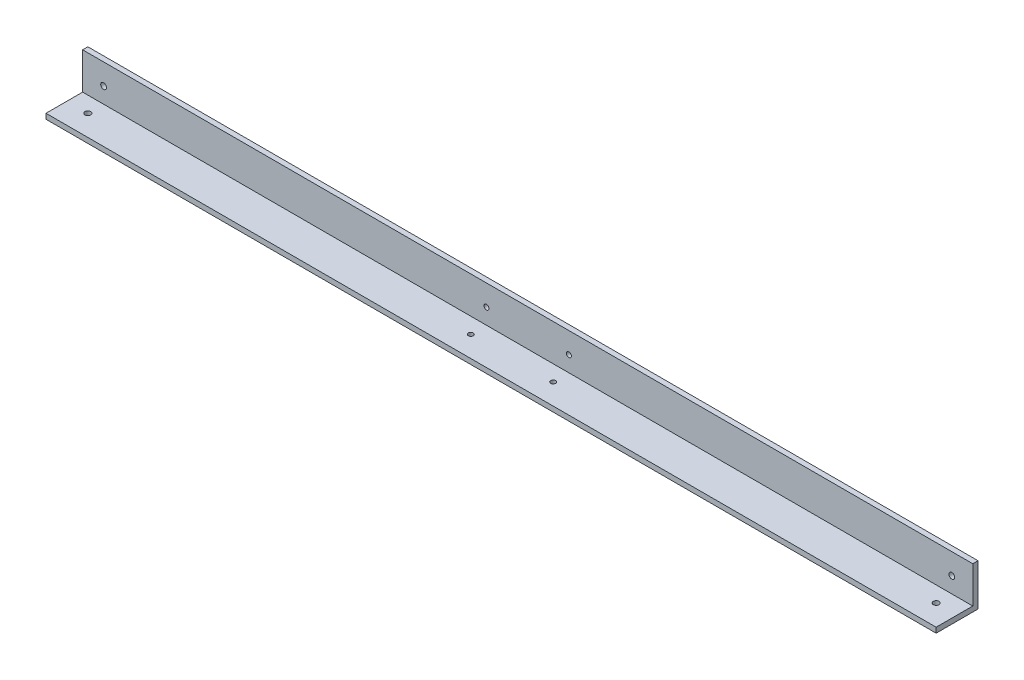
SolidWorks part; units mm, degrees
ref_plane "Alzado" through (0, 0, 0) normal (0, 0, 1) x (1, 0, 0)
ref_plane "Planta" through (0, 0, 0) normal (0, 1, 0) x (1, 0, 0)
ref_plane "Vista lateral" through (0, 0, 0) normal (1, 0, 0) x (0, 0, -1)
sketch "Croquis1" plane through (0, 0, 0) normal (1, 0, 0) x (0, 0, -1)
  line L0 (0, 25.4) -> (0, 0)
  line L1 (0, 0) -> (-25.4, 0)
  line L2 (-25.4, 0) -> (-25.4, 3.175)
  line L3 (-25.4, 3.175) -> (-3.175, 3.175)
  line L4 (-3.175, 3.175) -> (-3.175, 25.4)
  line L5 (-3.175, 25.4) -> (0, 25.4)
  dimension "D1" = 25.4
  dimension "D2" = 25.4
  dimension "D3" = 3.175
  dimension "D4" = 3.175
extrude "Saliente-Extruir1" add sketch "Croquis1" along normal blind 270 and the other way blind 270
ref_plane "Plano2" through (0, 0, 0) normal (0, -1, 0) x (-1, 0, 0)
sketch "Croquis3" plane through (0, 0, 0) normal (0, -1, 0) x (-1, 0, 0)
  line L0 (0, 0) -> (0, -25.4) construction
  line L1 (270, -25.4) -> (-270, -25.4) construction
  line L2 (-25, -12.7) -> (25, -12.7) construction
  line L3 (-270, -12.7) -> (-257.3, -12.7) construction
  line L4 (-270, -25.4) -> (-270, 0) construction
  circle A0 centre (-25, -12.7) radius 1.5
  circle A1 centre (25, -12.7) radius 1.5
  circle A2 centre (-257.3, -12.7) radius 1.75
  circle A3 centre (257.3, -12.7) radius 1.75
  point P8 (0, -12.7)
  dimension "D2" = 3
  dimension "D4" = 3.5
  dimension "D1" = 50
  dimension "D3" = 12.7
extrude "Cortar-Extruir1" cut sketch "Croquis3" against normal up to surface (3.175 mm away) up to face at (0, 3.175, 14.2875)
ref_plane "Plano3" through (0, 0, 0) normal (0, 0, -1) x (-1, 0, 0)
sketch "Croquis4" plane through (0, 0, 0) normal (0, 0, -1) x (-1, 0, 0)
  line L0 (0, 25.4) -> (0, 0) construction
  line L1 (270, 25.4) -> (-270, 25.4) construction
  line L2 (-25, 12.7) -> (25, 12.7) construction
  line L3 (-270, 12.7) -> (-257.3, 12.7) construction
  line L4 (-270, 0) -> (-270, 25.4) construction
  circle A0 centre (25, 12.7) radius 1.5
  circle A1 centre (-25, 12.7) radius 1.5
  circle A2 centre (-257.3, 12.7) radius 1.75
  circle A3 centre (257.3, 12.7) radius 1.75
  point P8 (0, 12.7)
  dimension "D2" = 3
  dimension "D4" = 3.5
  dimension "D1" = 50
  dimension "D3" = 12.7
extrude "Cortar-Extruir2" cut sketch "Croquis4" against normal up to surface (3.175 mm away) up to face at (0, 14.2875, 3.175)
